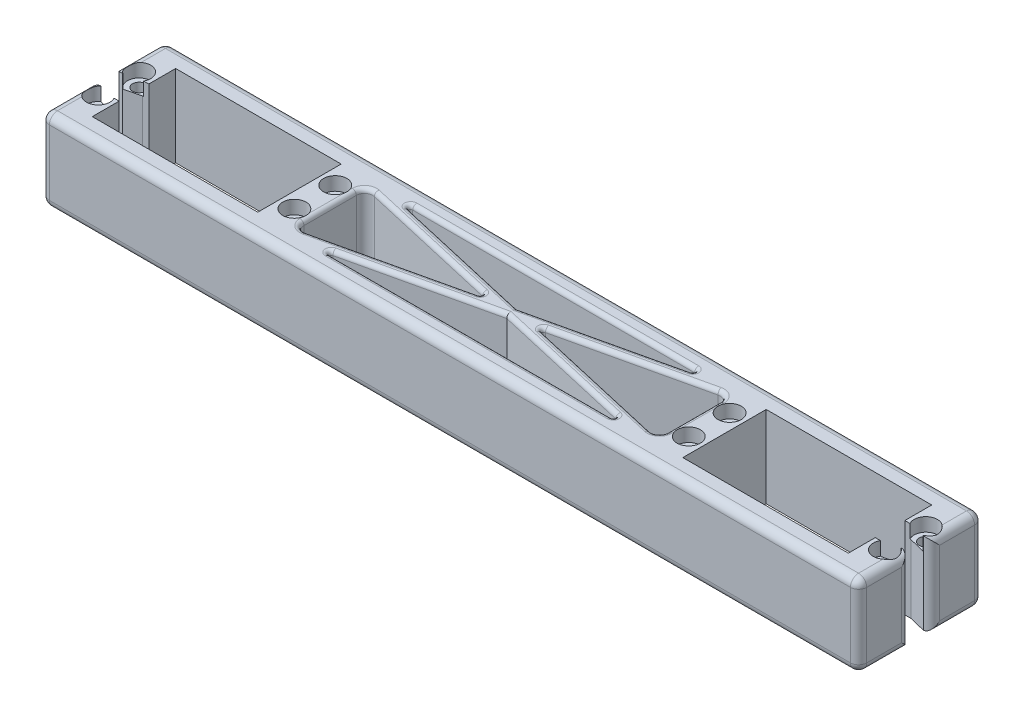
SolidWorks part; units mm, degrees
ref_plane "Front Plane" through (0, 0, 0) normal (0, 0, 1) x (1, 0, 0)
ref_plane "Top Plane" through (0, 0, 0) normal (0, 1, 0) x (1, 0, 0)
ref_plane "Right Plane" through (0, 0, 0) normal (1, 0, 0) x (0, 0, -1)
sketch "Sketch1" plane through (0, 0, 0) normal (0, 1, 0) x (1, 0, 0)
  line L1 (-27.75, -15.2) -> (172.25, -15.2)
  line L2 (-27.75, -15.2) -> (-27.75, 15.2)
  line L3 (-27.75, 15.2) -> (172.25, 15.2)
  line L4 (172.25, -15.2) -> (172.25, 15.2)
  point P0 (0, 0)
  point P6 (0, 0)
  point P7 (0, 0)
  point P8 (0, 0)
  point P9 (32.7872, 15.079)
  point P10 (-27.75, 0)
  dimension "D1" = 30.4
  dimension "D2" = 27.75
  dimension "D3" = 200
extrude "Boss-Extrude1" add sketch "Sketch1" along normal blind 20 contours L4 L3 L2 L1
sketch "Sketch2" plane through (0, 20, 0) normal (0, 1, 0) x (1, 0, 0)
  line L12 (-20.25, -10.2) -> (20.25, -10.2)
  line L13 (20.25, -10.2) -> (20.25, 10.2)
  line L14 (20.25, 10.2) -> (-20.25, 10.2)
  line L15 (-20.25, 10.2) -> (-20.25, -10.2)
  point P0 (0, 10.2)
  point P1 (20.25, 0)
  dimension "D2" = 20.4
  dimension "D1" = 40.5
extrude "Cut-Extrude1" cut sketch "Sketch2" against normal blind 20
sketch "Sketch3" plane through (0, 20, 0) normal (0, 1, 0) x (1, 0, 0)
  line L0 (-24, 5) -> (24, 5) construction
  line L1 (24, 5) -> (24, -5) construction
  line L2 (-24, 5) -> (-24, -5) construction
  circle A0 centre (-24, 5) radius 1.6
  circle A1 centre (-24, -5) radius 1.6
  circle A2 centre (24, -5) radius 1.6
  circle A3 centre (24, 5) radius 1.6
  point P2 (0, 5)
  point P5 (-24, 0)
  dimension "D3" = 3.2
  dimension "D1" = 10
  dimension "D2" = 48
extrude "Cut-Extrude2" cut sketch "Sketch3" against normal through all
sketch "Sketch4" plane through (0, 20, 0) normal (0, 1, 0) x (1, 0, 0)
  line L0 (-20.25, 3.625) -> (-20.25, -3.625)
  line L1 (-20.25, -3.625) -> (-21.75, -3.625)
  line L2 (-21.75, -3.625) -> (-25.75, -2.65)
  line L4 (-25.75, 2.65) -> (-21.75, 3.625)
  line L5 (-21.75, 3.625) -> (-20.25, 3.625)
  line L6 (-20.25, 10.2) -> (-20.25, -10.2) construction
  line L8 (-25.75, 2.65) -> (-27.75, 2.65)
  line L9 (-27.75, 2.65) -> (-27.75, -2.65)
  line L10 (-27.75, -2.65) -> (-25.75, -2.65)
  line L11 (-27.75, -15.2) -> (-27.75, 15.2) construction
  point P2 (-24, 2.65)
  point P7 (-20.25, 0)
  point P10 (0, 0)
  point P15 (0, 0)
  point P17 (-27.75, 0)
  point P19 (-25.6176, -2.65)
  point P20 (0, 0)
  point P21 (-21.75, -3.5612)
  dimension "D1" = 7.25
  dimension "D2" = 1.5
  dimension "D3" = 5.3
  dimension "D4" = 2
extrude "Cut-Extrude3" cut sketch "Sketch4" against normal through all
sketch "Sketch5" plane through (0, 20, 0) normal (0, 1, 0) x (1, 0, 0)
  line L0 (72.25, 15.2) -> (72.25, -15.2) construction
  line L1 (-27.75, 15.2) -> (172.25, 15.2) construction
  line L2 (-27.75, -15.2) -> (172.25, -15.2) construction
  line L3 (164.75, 3.625) -> (164.75, 10.2)
  line L4 (166.25, 3.625) -> (164.75, 3.625)
  line L5 (170.25, 2.65) -> (166.25, 3.625)
  line L6 (172.25, 2.65) -> (170.25, 2.65)
  line L7 (170.25, -2.65) -> (172.25, -2.65)
  line L8 (166.25, -3.625) -> (170.25, -2.65)
  line L9 (164.75, -3.625) -> (166.25, -3.625)
  line L10 (164.75, -10.2) -> (164.75, -3.625)
  line L11 (164.75, 10.2) -> (124.25, 10.2)
  line L12 (124.25, -10.2) -> (164.75, -10.2)
  line L13 (124.25, 10.2) -> (124.25, -10.2)
  line L14 (-27.75, 2.65) -> (-27.75, -2.65)
  line L15 (172.25, 2.65) -> (172.25, -2.65)
  line L16 (-20.25, -3.625) -> (-21.75, -3.625)
  line L17 (-21.75, -3.625) -> (-25.75, -2.65)
  line L18 (-25.75, -2.65) -> (-27.75, -2.65)
  line L19 (-27.75, -2.65) -> (-27.75, -15.2)
  line L20 (-27.75, -15.2) -> (172.25, -15.2)
  line L21 (172.25, -15.2) -> (172.25, 15.2)
  line L22 (172.25, 15.2) -> (-27.75, 15.2)
  line L23 (-27.75, 15.2) -> (-27.75, 2.65)
  line L24 (-27.75, 2.65) -> (-25.75, 2.65)
  line L25 (-25.75, 2.65) -> (-21.75, 3.625)
  line L26 (-21.75, 3.625) -> (-20.25, 3.625)
  line L27 (-20.25, 3.625) -> (-20.25, 10.2)
  line L28 (-20.25, 10.2) -> (20.25, 10.2)
  line L29 (20.25, 10.2) -> (20.25, -10.2)
  line L30 (20.25, -10.2) -> (-20.25, -10.2)
  line L31 (-20.25, -10.2) -> (-20.25, -3.625)
  line L32 (-20.25, -3.625) -> (-21.75, -3.625)
  line L33 (-21.75, -3.625) -> (-25.75, -2.65)
  line L34 (-25.75, -2.65) -> (-27.75, -2.65)
  line L40 (-27.75, 2.65) -> (-25.75, 2.65)
  line L41 (-25.75, 2.65) -> (-21.75, 3.625)
  line L42 (-21.75, 3.625) -> (-20.25, 3.625)
  line L43 (-20.25, 3.625) -> (-20.25, 10.2)
  line L44 (-20.25, 10.2) -> (20.25, 10.2)
  line L45 (20.25, 10.2) -> (20.25, -10.2)
  line L46 (20.25, -10.2) -> (-20.25, -10.2)
  line L47 (-20.25, -10.2) -> (-20.25, -3.625)
  circle A0 centre (-24, -5) radius 1.6 construction
  circle A1 centre (24, -5) radius 1.6 construction
  circle A2 centre (24, 5) radius 1.6 construction
  circle A3 centre (-24, 5) radius 1.6 construction
  circle A4 centre (-24, -5) radius 1.6
  circle A5 centre (24, -5) radius 1.6
  circle A6 centre (24, 5) radius 1.6
  circle A7 centre (-24, 5) radius 1.6
  circle A8 centre (168.5, 5) radius 1.6
  circle A9 centre (168.5, -5) radius 1.6
  circle A10 centre (120.5, 5) radius 1.6
  circle A11 centre (120.5, -5) radius 1.6
  dimension "D1" = 0
extrude "Cut-Extrude4" cut sketch "Sketch5" against normal through all
sketch "Sketch6" plane through (0, 20, 0) normal (0, 1, 0) x (1, 0, 0)
  line L0 (124.25, 10.2) -> (124.25, -10.2) construction
  line L1 (27.75, -10.2) -> (116.75, -10.2)
  line L2 (27.75, -10.2) -> (27.75, 10.2)
  line L3 (27.75, 10.2) -> (116.75, 10.2)
  line L4 (116.75, -10.2) -> (116.75, 10.2)
  line L5 (27.75, -10.2) -> (116.75, 10.2) construction
  line L6 (27.75, 10.2) -> (116.75, -10.2) construction
  line L7 (-27.75, 15.2) -> (172.25, 15.2) construction
  point P0 (72.25, 0)
  point P7 (72.0663, -6.384)
  point P10 (72.25, 15.2)
  point P11 (72.25, -0.5971)
  point P12 (0, 0)
  point P14 (27.75, 9.9664)
  point P17 (0, 0)
  dimension "D1" = 7.5
extrude "Cut-Extrude5" cut sketch "Sketch6" against normal through all
sketch "Sketch7" plane through (0, 20, 0) normal (0, 1, 0) x (1, 0, 0)
  line L0 (27.75, -10.2) -> (116.75, 10.2) construction
  line L1 (116.75, -10.2) -> (27.75, 10.2) construction
  line L3 (27.75, 10.2) -> (27.75, -10.2) construction
  line L4 (27.75, -8.9176) -> (66.6551, 0)
  line L6 (33.3449, -10.2) -> (72.25, -1.2824)
  line L7 (27.75, -10.2) -> (116.75, -10.2) construction
  line L8 (33.3449, -10.2) -> (27.75, -10.2)
  line L9 (27.75, -10.2) -> (27.75, -8.9176)
  line L10 (27.75, 0) -> (116.75, 0) construction
  line L11 (116.75, -10.2) -> (116.75, 10.2) construction
  line L12 (72.25, 10.2) -> (72.25, -10.2) construction
  line L13 (116.75, 10.2) -> (27.75, 10.2) construction
  line L14 (27.75, 8.9176) -> (66.6551, 0)
  line L15 (27.75, 10.2) -> (27.75, 8.9176)
  line L16 (33.3449, 10.2) -> (27.75, 10.2)
  line L17 (33.3449, 10.2) -> (72.25, 1.2824)
  line L18 (111.1551, -10.2) -> (72.25, -1.2824)
  line L19 (111.1551, -10.2) -> (116.75, -10.2)
  line L20 (116.75, -8.9176) -> (77.8449, 0)
  line L21 (116.75, -10.2) -> (116.75, -8.9176)
  line L22 (111.1551, 10.2) -> (72.25, 1.2824)
  line L23 (116.75, 10.2) -> (116.75, 8.9176)
  line L24 (111.1551, 10.2) -> (116.75, 10.2)
  line L25 (116.75, 8.9176) -> (77.8449, 0)
  point P13 (72.25, 0)
  dimension "D1" = 1.25
  dimension "D2" = 1.25
extrude "Boss-Extrude2" add sketch "Sketch7" against normal up to surface (20 mm away) up to face at (72.25, 0, 0)
fillet "Fillet1" radius 2 24 edges at (172.25, 0, -8.925) (172.25, 10, -2.65) (172.25, 20, -8.925) (172.25, 20, 8.925) (172.25, 10, 2.65) (172.25, 0, 8.925) (-27.75, 0, -8.925) (-27.75, 20, -8.925) (-27.75, 10, -2.65) (-27.75, 20, 8.925) (-27.75, 0, 8.925) (-27.75, 10, 2.65) (172.25, 10, -15.2) (72.25, 20, -15.2) (-27.75, 10, -15.2) (72.25, 0, -15.2) (-27.75, 10, 15.2) (72.25, 20, 15.2) (172.25, 10, 15.2) (72.25, 0, 15.2) (27.75, 10, 8.9176) (27.75, 10, -8.9176) (116.75, 10, -8.9176) (116.75, 10, 8.9176)
fillet "Fillet2" radius 0.5 6 edges at (33.3449, 10, -10.2) (33.3449, 10, 10.2) (111.1551, 10, 10.2) (111.1551, 10, -10.2) (77.8449, 10, 0) (66.6551, 10, 0)
fillet "Fillet3" radius 1 44 edges at (115.9963, 0, 7.9715) (97.1371, 0, 4.422) (79.5828, 0, 0) (97.1371, 0, -4.422) (115.9963, 0, -7.9715) (89.5488, 0, -5.2475) (107.2327, 0, -9.7562) (54.9512, 0, -5.2475) (37.2673, 0, -9.7562) (27.75, 0, 0) (28.5037, 0, -7.9715) (47.3629, 0, -4.422) (64.9172, 0, 0) (47.3629, 0, 4.422) (54.9512, 0, 5.2475) (37.2673, 0, 9.7562) (89.5488, 0, 5.2475) (107.2327, 0, 9.7562) (54.9512, 20, 5.2475) (37.2673, 20, 9.7562) (72.25, 20, 10.2) (107.2327, 20, 9.7562) (79.5828, 20, 0) (97.1371, 20, 4.422) (115.9963, 20, 7.9715) (116.75, 20, 0) (115.9963, 20, -7.9715) (89.5488, 20, -5.2475) (107.2327, 20, -9.7562) (72.25, 20, -10.2) (37.2673, 20, -9.7562) (28.5037, 20, -7.9715) (27.75, 20, 0) (28.5037, 20, 7.9715) (47.3629, 20, 4.422) (64.9172, 20, 0) (116.75, 0, 0) (72.25, 0, -10.2) (28.5037, 0, 7.9715) (72.25, 0, 10.2) (89.5488, 20, 5.2475) (97.1371, 20, -4.422) (54.9512, 20, -5.2475) (47.3629, 20, -4.422)
sketch "Sketch8" plane through (0, 20, 0) normal (0, 1, 0) x (1, 0, 0)
  circle A27 centre (-24, 5) radius 2.85
  circle A28 centre (-24, -5) radius 2.85
  circle A29 centre (24, 5) radius 2.85
  circle A30 centre (24, -5) radius 2.85
  circle A31 centre (120.5, 5) radius 2.85
  circle A32 centre (120.5, -5) radius 2.85
  circle A33 centre (168.5, 5) radius 2.85
  circle A34 centre (168.5, -5) radius 2.85
  circle A35 centre (-24, 5) radius 1.6 construction
  circle A36 centre (-24, -5) radius 1.6 construction
  circle A37 centre (24, 5) radius 1.6 construction
  circle A38 centre (24, -5) radius 1.6 construction
  circle A39 centre (120.5, 5) radius 1.6 construction
  circle A40 centre (120.5, -5) radius 1.6 construction
  circle A41 centre (168.5, 5) radius 1.6 construction
  circle A42 centre (168.5, -5) radius 1.6 construction
  dimension "D1" = 5.7
extrude "Cut-Extrude6" cut sketch "Sketch8" against normal blind 3.3
